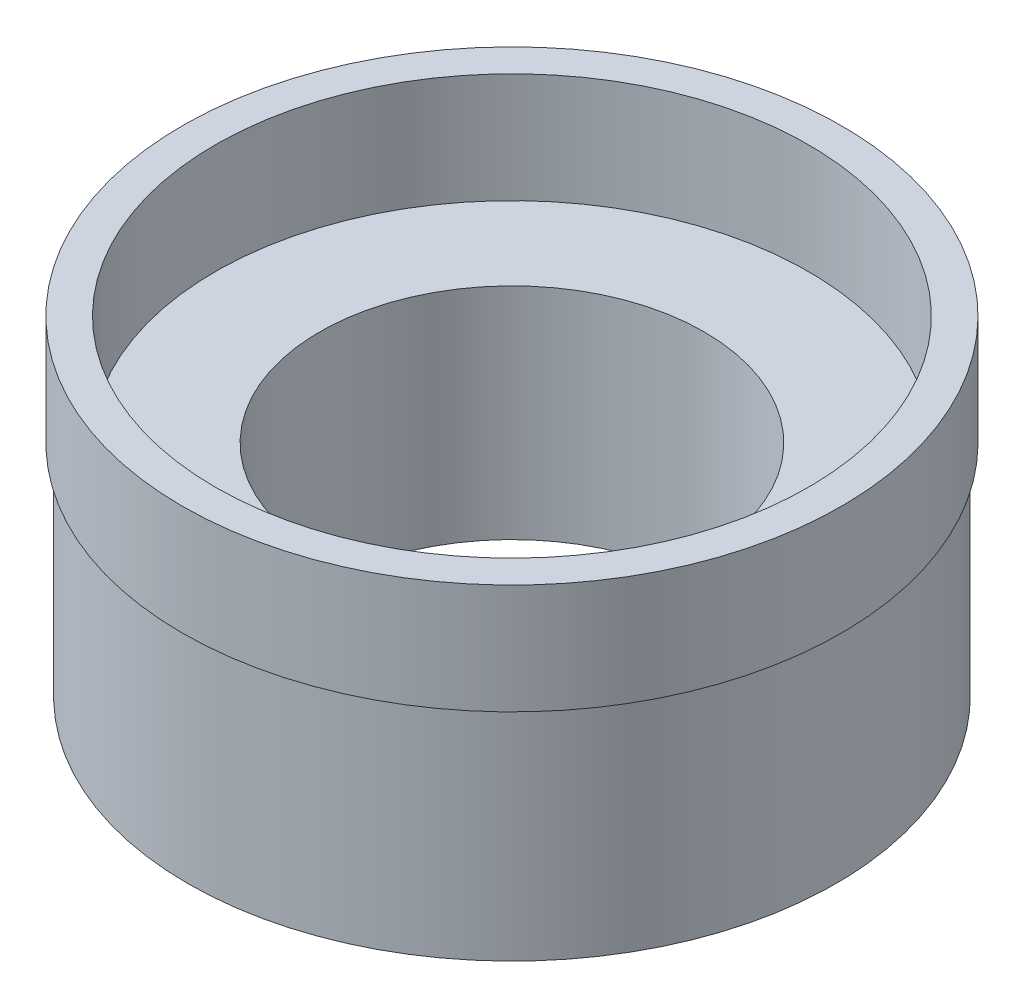
SolidWorks part; units mm, degrees
ref_plane "Front Plane" through (0, 0, 0) normal (0, 0, 1) x (1, 0, 0)
ref_plane "Top Plane" through (0, 0, 0) normal (0, 1, 0) x (1, 0, 0)
ref_plane "Right Plane" through (0, 0, 0) normal (1, 0, 0) x (0, 0, -1)
sketch "Sketch1" plane through (0, 0, 0) normal (0, 1, 0) x (1, 0, 0)
  circle A0 centre (0, 0) radius 38.1
  circle A1 centre (0, 0) radius 34.29
  dimension "D1" = 76.2
  dimension "D2" = 68.58
extrude "Boss-Extrude1" add sketch "Sketch1" along normal blind 12.7
sketch "Sketch2" plane through (0, 0, 0) normal (0, -1, 0) x (1, 0, 0)
  circle A0 centre (0, 0) radius 37.465
  circle A1 centre (0, 0) radius 22.225
  dimension "D1" = 74.93
  dimension "D2" = 44.45
extrude "Boss-Extrude2" add sketch "Sketch2" along normal blind 25.4
